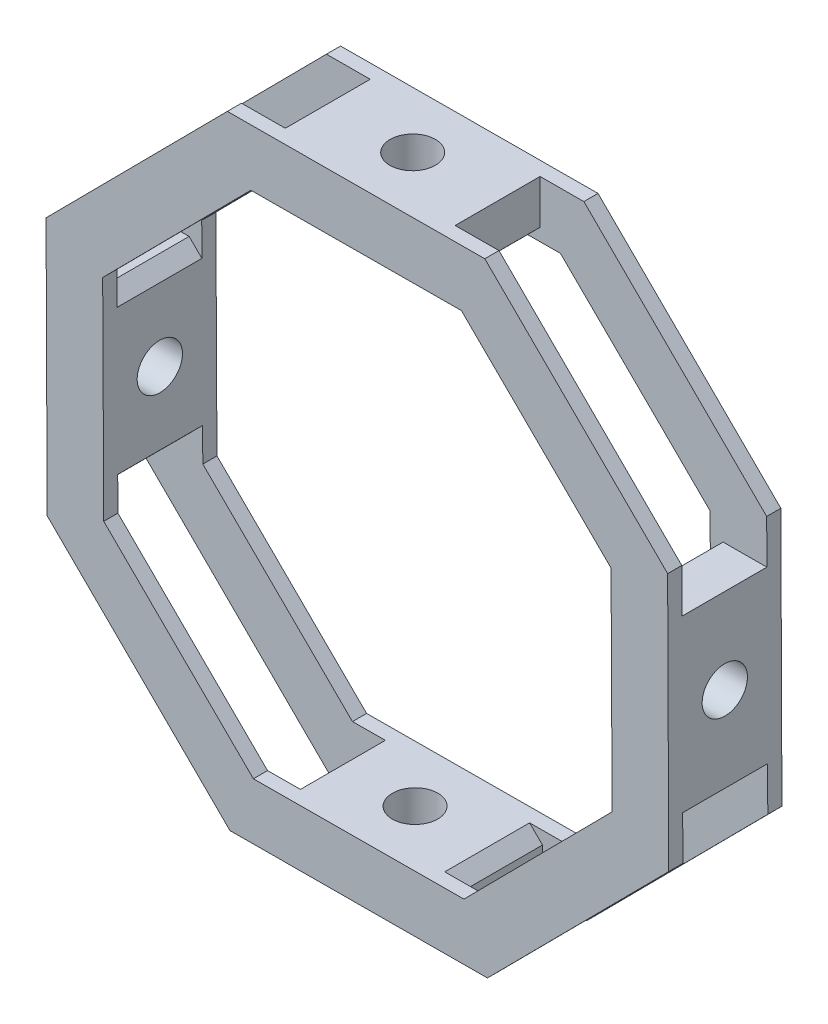
SolidWorks part; units mm, degrees
ref_plane "Plano frontal" through (0, 0, 0) normal (0, 0, 1) x (1, 0, 0)
ref_plane "Plano superior" through (0, 0, 0) normal (0, 1, 0) x (1, 0, 0)
ref_plane "Plano direito" through (0, 0, 0) normal (1, 0, 0) x (0, 0, -1)
sketch "Esboço1" plane through (0, 0, 0) normal (0, 0, 1) x (1, 0, 0)
  line L1 (109.614, 45.9495) -> (45.0177, 110)
  line L2 (45.0177, 110) -> (-45.9495, 109.614)
  line L3 (-45.9495, 109.614) -> (-110, 45.0177)
  line L4 (-110, 45.0177) -> (-109.614, -45.9495)
  line L5 (-109.614, -45.9495) -> (-45.0177, -110)
  line L6 (-45.0177, -110) -> (45.9495, -109.614)
  line L7 (45.9495, -109.614) -> (110, -45.0177)
  line L8 (110, -45.0177) -> (109.614, 45.9495)
  line L9 (89.6222, 37.657) -> (36.7449, 90)
  line L10 (36.7449, 90) -> (-37.657, 89.6222)
  line L11 (-37.657, 89.6222) -> (-90, 36.7449)
  line L12 (-90, 36.7449) -> (-89.6222, -37.657)
  line L13 (-89.6222, -37.657) -> (-36.7449, -90)
  line L14 (-36.7449, -90) -> (37.657, -89.6222)
  line L15 (37.657, -89.6222) -> (90, -36.7449)
  line L16 (90, -36.7449) -> (89.6222, 37.657)
  circle A0 centre (0, 0) radius 109.808 construction
  circle A1 centre (0, 0) radius 89.8123 construction
extrude "Ressalto-extrusão1" add sketch "Esboço1" along normal blind 40
sketch "Esboço2" plane through (109.807, 0.4659, 0) normal (1, 0.0042, 0) x (0, 0, -1)
  line L0 (-40, -45.484) -> (-40, 45.484) construction
  line L1 (0, 0) -> (-40, 0)
  line L2 (0, 0) -> (0, 30)
  line L3 (0, 30) -> (-40, 30)
  line L4 (-40, 0) -> (-40, 30)
  line L5 (-40, -45.484) -> (0, -45.484) construction
  line L6 (0, 0) -> (-40, 0)
  line L7 (0, 0) -> (0, -30)
  line L8 (0, -30) -> (-40, -30)
  line L9 (-40, 0) -> (-40, -30)
  line L10 (0, 45.484) -> (-5, 45.484)
  line L11 (0, 45.484) -> (0, 30)
  line L12 (0, 30) -> (-5, 30)
  line L13 (-5, 45.484) -> (-5, 30)
  line L14 (-40, 45.484) -> (-35, 45.484)
  line L15 (-40, 45.484) -> (-40, 30)
  line L16 (-40, 30) -> (-35, 30)
  line L17 (-35, 45.484) -> (-35, 30)
  line L18 (-5, -30) -> (-35, -30)
  line L19 (-5, -30) -> (-5, -45.484)
  line L20 (-5, -45.484) -> (-35, -45.484)
  line L21 (-35, -30) -> (-35, -45.484)
  circle A0 centre (-20, 0) radius 8
  line M2 (0, 45.484) -> (-40, 45.484)
  line M4 (-40, -45.484) -> (0, -45.484)
extrude "Corte-extrusão1" cut sketch "Esboço2" against normal through all both and the other way through all contours L17 L3 L13 M2 | L8 L21 L19 M4 | L6 A0 | L6 A0 region at (109.8214, -2.9294, 20) region at (109.7926, 3.8612, 20) region at (109.6469, 38.2075, 20) region at (109.9672, -37.2757, 20)
sketch "Esboço3" plane through (-0.4659, 109.807, 0) normal (-0.0042, 1, 0) x (1, 0.0042, 0)
  line L0 (45.484, -40) -> (-45.484, -40) construction
  line L1 (0, 0) -> (30, 0)
  line L2 (0, 0) -> (0, -40)
  line L3 (0, -40) -> (30, -40)
  line L4 (30, 0) -> (30, -40)
  line L5 (45.484, -40) -> (45.484, 0) construction
  line L6 (0, 0) -> (-30, 0)
  line L7 (0, 0) -> (0, -40)
  line L8 (0, -40) -> (-30, -40)
  line L9 (-30, 0) -> (-30, -40)
  line L10 (-45.484, 0) -> (-30, 0)
  line L11 (-45.484, 0) -> (-45.484, -5)
  line L12 (-45.484, -5) -> (-30, -5)
  line L13 (-30, 0) -> (-30, -5)
  line L14 (-45.484, -40) -> (-30, -40)
  line L15 (-45.484, -40) -> (-45.484, -35)
  line L16 (-45.484, -35) -> (-30, -35)
  line L17 (-30, -40) -> (-30, -35)
  line L18 (30, -35) -> (45.484, -35)
  line L19 (30, -35) -> (30, -5)
  line L20 (30, -5) -> (45.484, -5)
  line L21 (45.484, -35) -> (45.484, -5)
  circle A0 centre (0, -20) radius 8
  line M2 (-45.484, 0) -> (-45.484, -40)
  line M4 (45.484, -40) -> (45.484, 0)
extrude "Corte-extrusão2" cut sketch "Esboço3" against normal through all both and the other way through all contours L7 A0 | L7 A0 | L20 L4 L18 M4 | L16 L9 L12 M2 region at (2.9294, 109.8214, 20) region at (-3.8612, 109.7926, 20) region at (37.2757, 109.9672, 20) region at (-38.2075, 109.6469, 20)
sketch "Esboço4" plane through (77.3159, 77.9747, 0) normal (0.7041, 0.7101, 0) x (0, 0, -1)
  line L0 (-35, -45.484) -> (-5, -45.484) construction
  line L1 (-35, 45.484) -> (-5, 45.484)
  line L2 (-35, 45.484) -> (-35, -45.484)
  line L3 (-35, -45.484) -> (-5, -45.484)
  line L4 (-5, 45.484) -> (-5, -45.484)
extrude "Corte-extrusão3" cut sketch "Esboço4" against normal through all both and the other way through all
sketch "Esboço5" plane through (-77.9747, 77.3159, 0) normal (-0.7101, 0.7041, 0) x (0, 0, 1)
  line L1 (35, 45.484) -> (5, 45.484)
  line L2 (35, 45.484) -> (35, -45.484)
  line L3 (35, -45.484) -> (5, -45.484)
  line L4 (5, 45.484) -> (5, -45.484)
extrude "Corte-extrusão4" cut sketch "Esboço5" against normal through all both and the other way through all
